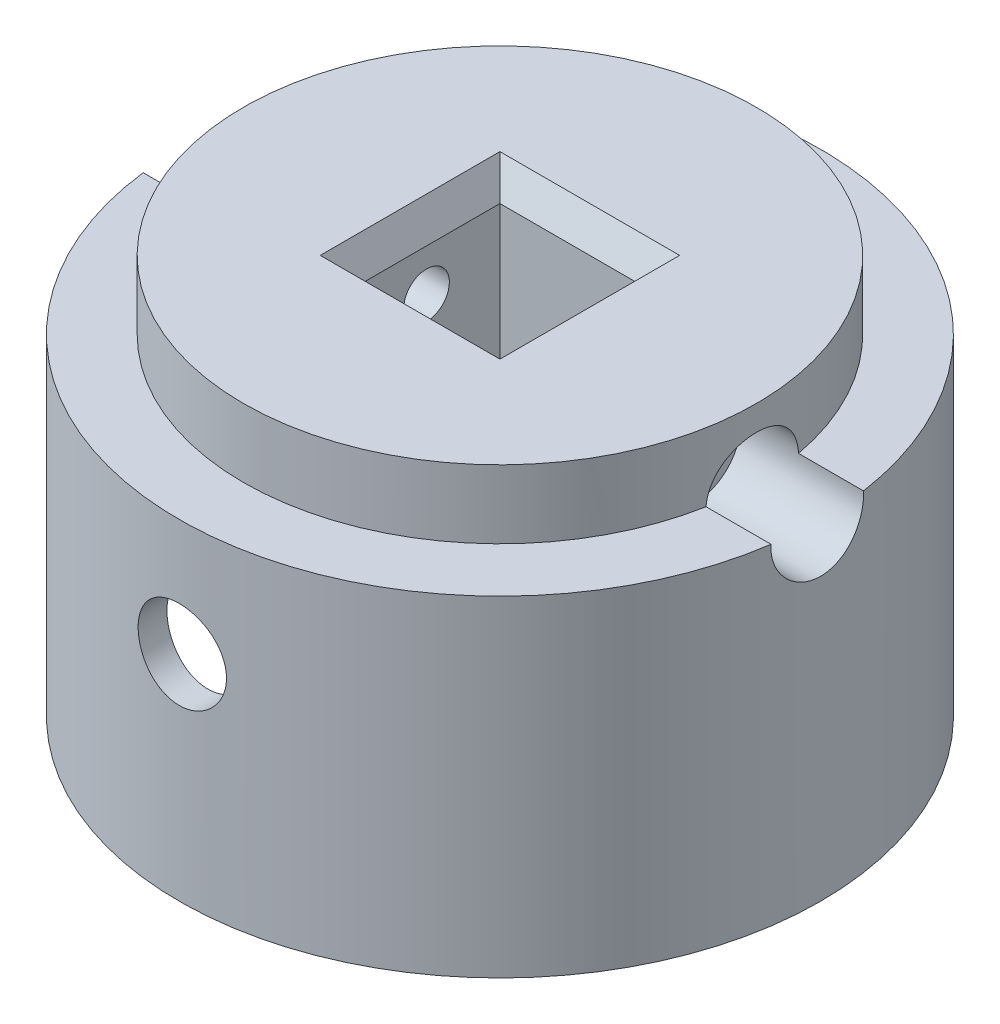
SolidWorks part; units mm, degrees
ref_plane "Спереди" through (0, 0, 0) normal (0, 0, 1) x (1, 0, 0)
ref_plane "Сверху" through (0, 0, 0) normal (0, 1, 0) x (1, 0, 0)
ref_plane "Справа" through (0, 0, 0) normal (1, 0, 0) x (0, 0, -1)
sketch "Sketch1" plane through (0, 0, 0) normal (0, 1, 0) x (1, 0, 0)
  circle A0 centre (0, 0) radius 22.5
  dimension "D1" = 45
extrude "Boss-Extrude1" add sketch "Sketch1" along normal blind 28
sketch "Sketch2" plane through (0, 0, 0) normal (0, -1, 0) x (1, 0, 0)
  line L1 (5.15, 5.15) -> (-5.15, 5.15)
  line L2 (5.15, 5.15) -> (5.15, -5.15)
  line L3 (5.15, -5.15) -> (-5.15, -5.15)
  line L4 (-5.15, 5.15) -> (-5.15, -5.15)
  line L5 (5.15, 5.15) -> (-5.15, -5.15) construction
  line L6 (5.15, -5.15) -> (-5.15, 5.15) construction
  point P0 (0, 0)
  dimension "D1" = 10.3
extrude "Cut-Extrude2" cut sketch "Sketch2" against normal through all
shell "Shell3" thickness 2 removed face at (0, 0, 0)
sketch "Sketch3" plane through (0, 0, 7.15) normal (0, 0, 1) x (1, 0, 0)
  line L0 (0, 26) -> (0, 0) construction
  line L1 (7.15, 26) -> (-7.15, 26) construction
  line L2 (7.15, 0) -> (-7.15, 0) construction
  line L3 (-22.5, 0) -> (22.5, 0) construction
  circle A0 centre (0, 15) radius 3.1
  dimension "D1" = 6.2
  dimension "D2" = 15
extrude "Cut-Extrude3" cut sketch "Sketch3" along normal through all
chamfer "Chamfer1" distance 2 angle 30 4 edges at (-5.15, 28, 0) (0, 28, 5.15) (5.15, 28, 0) (0, 28, -5.15) first distance on face at (-5.15, 14, 0) first distance on face at (0, 14, 5.15) first distance on face at (5.15, 14, 0) first distance on face at (0, 14, -5.15)
sketch "Sketch18" plane through (0, 26, 0) normal (0, -1, 0) x (1, 0, 0)
  line L0 (0, 0) -> (-18.4253, -8.9866) construction
  line L1 (0, 0) -> (-17.385, 10.8633) construction
  line L2 (0, 0) -> (0, -20.5) construction
  line L3 (-15.7289, -7.6715) -> (-18.4253, -8.9866)
  line L4 (-14.8408, 9.2736) -> (-17.385, 10.8633)
  circle A0 centre (0, 0) radius 20.5 construction
  arc A1 (-18.4253, -8.9866) -> (-17.385, 10.8633) centre (0, 0) cw
  arc A2 (-14.8408, 9.2736) -> (-15.7289, -7.6715) centre (0, 0) ccw
  dimension "D1" = 64
  dimension "D2" = 58
  dimension "D3" = 3
extrude "Boss-Extrude8" add sketch "Sketch18" along normal offset from surface (23 mm away) 3 up to face at (0, 0, 20.5)
sketch "Sketch9" plane through (0, 0, 0) normal (0, -1, 0) x (1, 0, 0)
  line L0 (0, -7.15) -> (0, -20.5) construction
  line L2 (2.0571, -22.4058) -> (-16.5967, -15.1921)
  line L3 (-16.5967, -15.1921) -> (-17.6788, -17.9902)
  line L4 (-17.6788, -17.9902) -> (0.975, -25.2038)
  line L5 (0.975, -25.2038) -> (2.0571, -22.4058)
  line L6 (-7.15, -7.15) -> (7.15, -7.15) construction
  line L7 (2.0571, -22.4058) -> (0, -7.15) construction
  circle A0 centre (0, 0) radius 22.5 construction
  circle A1 centre (0, 0) radius 20.5 construction
  dimension "D1" = 20
  dimension "D2" = 3
  dimension "D3" = 7.679
extrude "Boss-Extrude4" add sketch "Sketch9" against normal blind 20
sketch "Sketch11" plane through (0, 0, 0) normal (0, -1, 0) x (1, 0, 0)
  line L0 (2.0571, -22.4058) -> (7.15, -7.15)
  line L1 (7.15, -7.15) -> (-7.15, -7.15)
  line L2 (-7.15, -7.15) -> (-16.5967, -15.1921)
  line L3 (-16.5967, -15.1921) -> (2.0571, -22.4058) construction
  line L4 (-3.78, -20.1485) -> (-10.7596, -17.4494) construction
  arc A0 (2.0571, -22.4058) -> (-16.5967, -15.1921) centre (0, 0) ccw construction
  arc A1 (2.0571, -22.4058) -> (-16.5967, -15.1921) centre (0, 0) cw
  arc A2 (2.0571, -22.4058) -> (-16.5967, -15.1921) centre (0, 0) ccw construction
  point P4 (-7.2698, -18.7989)
extrude "Boss-Extrude6" add sketch "Sketch11" against normal up to surface (26 mm away) up to face at (0, 26, 0)
sketch "Sketch12" plane through (0, 0, 0) normal (0, -1, 0) x (1, 0, 0)
  line L0 (-7.15, -7.15) -> (-15.0727, -13.8947) construction
  line L1 (2.7554, -20.314) -> (7.15, -7.15) construction
  line L2 (3.8359, -17.0772) -> (2.7554, -20.314)
  line L3 (-15.0727, -13.8947) -> (-12.7884, -11.95)
  arc A0 (2.7554, -20.314) -> (-15.0727, -13.8947) centre (0, 0) cw
  arc A1 (-12.7884, -11.95) -> (3.8359, -17.0772) centre (0, 0) ccw
  arc A2 (2.7554, -20.314) -> (-15.0727, -13.8947) centre (0, 0) ccw construction
  dimension "D1" = 3
extrude "Cut-Extrude5" cut sketch "Sketch12" against normal blind 12
sketch "Sketch13" plane through (-8.3519, 0, -21.597) normal (-0.3607, 0, -0.9327) x (-0.9327, 0, 0.3607)
  line L0 (0, 20) -> (0, 0) construction
  line L1 (10, 20) -> (-10, 20) construction
  line L2 (10, 0) -> (-10, 0) construction
  circle A0 centre (0, 10) radius 3.8
  dimension "D1" = 7.6
extrude "Cut-Extrude6" cut sketch "Sketch13" against normal blind 16
sketch "Sketch15" plane through (-8.3519, 0, -21.597) normal (-0.3607, 0, -0.9327) x (-0.9327, 0, 0.3607)
  line L0 (-10, 10) -> (10, 10) construction
  line L1 (-10, 20) -> (-10, 0) construction
  line L2 (10, 20) -> (10, 0) construction
  line L4 (5, 11.5) -> (-5, 11.5)
  line L5 (5, 11.5) -> (5, 8.5)
  line L6 (5, 8.5) -> (-5, 8.5)
  line L7 (-5, 11.5) -> (-5, 8.5)
  line L8 (5, 11.5) -> (-5, 8.5) construction
  line L9 (5, 8.5) -> (-5, 11.5) construction
  point P6 (0, 10)
  dimension "D1" = 10
  dimension "D2" = 3
extrude "Cut-Extrude8" cut sketch "Sketch15" against normal blind 16
sketch "Sketch17" plane through (0, 0, 0) normal (0, -1, 0) x (1, 0, 0)
  line L0 (7.15, 7.15) -> (7.15, -7.15)
  line L1 (7.15, -7.15) -> (3.8359, -17.0772)
  line L2 (7.15, 7.15) -> (-7.15, 7.15)
  line L3 (-7.15, 7.15) -> (-7.15, -7.15)
  line L4 (-7.15, -7.15) -> (-12.7884, -11.95)
  arc A0 (3.8359, -17.0772) -> (-12.7884, -11.95) centre (0, 0) cw
  arc A1 (-12.7884, -11.95) -> (3.8359, -17.0772) centre (0, 0) ccw construction
extrude "Cut-Extrude9" cut sketch "Sketch17" against normal blind 2
sketch "Sketch20" plane through (0, 26, 0) normal (0, -1, 0) x (1, 0, 0)
  line L0 (2.7554, -20.314) -> (7.15, -7.15)
  line L1 (7.15, -7.15) -> (7.15, 7.15)
  line L2 (7.15, 7.15) -> (-7.15, 7.15)
  line L3 (-7.15, 7.15) -> (-7.15, -7.15)
  line L4 (-7.15, -7.15) -> (-15.0727, -13.8947)
  arc A0 (2.7554, -20.314) -> (-15.0727, -13.8947) centre (0, 0) ccw
  arc A1 (2.7554, -20.314) -> (-17.385, 10.8633) centre (0, 0) ccw construction
extrude "Boss-Extrude10" add sketch "Sketch20" along normal blind 7
sketch "Sketch21" plane through (0, 28, 0) normal (0, 1, 0) x (1, 0, 0)
  circle A0 centre (0, 0) radius 18
  dimension "D1" = 36
extrude "Cut-Extrude11" cut sketch "Sketch21" against normal blind 4.8 flip side to cut
sketch "Sketch22" plane through (5.15, 0, 0) normal (-1, 0, 0) x (0, 0, 1)
  line L0 (0, 26) -> (0, 2) construction
  line L1 (5.15, 26) -> (-5.15, 26) construction
  line L2 (-5.15, 2) -> (5.15, 2) construction
  line L3 (-6.3047, 28) -> (6.3047, 28) construction
  circle A0 centre (0, 23) radius 1.6
  point P10 (0, 28)
  dimension "D1" = 3.2
  dimension "D2" = 5
extrude "Cut-Extrude12" cut sketch "Sketch22" against normal through all both and the other way through all
sketch "Sketch24" plane through (5.15, 0, 0) normal (-1, 0, 0) x (0, 0, 1)
  circle A0 centre (0, 23) radius 3.25
  dimension "D1" = 6.5
extrude "Cut-Extrude13" cut sketch "Sketch24" against normal through all from offset 8.5 offset against normal yes
sketch "Sketch25" plane through (-5.15, 0, 0) normal (1, 0, 0) x (0, 0, -1)
  line L0 (-5.15, 26) -> (-5.15, 2) construction
  line L1 (0, 19.8936) -> (2.6903, 21.4468)
  line L2 (2.6903, 21.4468) -> (2.6903, 24.5532)
  line L3 (2.6903, 24.5532) -> (0, 26.1064)
  line L4 (0, 26.1064) -> (-2.6903, 24.5532)
  line L5 (-2.6903, 24.5532) -> (-2.6903, 21.4468)
  line L6 (-2.6903, 21.4468) -> (0, 19.8936)
  circle A0 centre (0, 23) radius 3.1064 construction
extrude "Cut-Extrude14" cut sketch "Sketch25" against normal through all from offset 8.5 offset against normal yes
